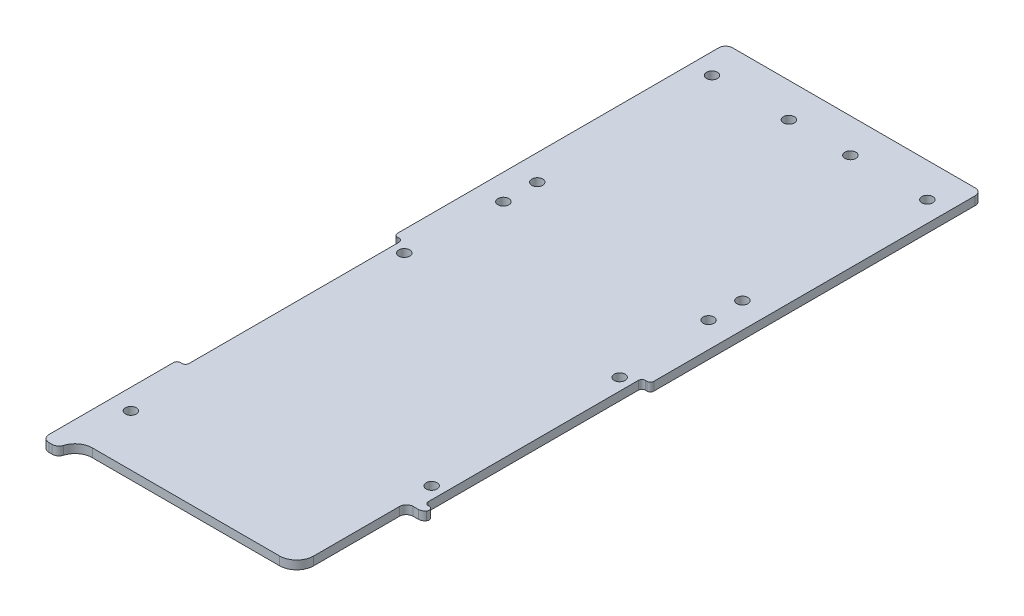
SolidWorks part; units mm, degrees
ref_plane "Front Plane" through (0, 0, 0) normal (0, 0, 1) x (1, 0, 0)
ref_plane "Top Plane" through (0, 0, 0) normal (0, 1, 0) x (1, 0, 0)
ref_plane "Right Plane" through (0, 0, 0) normal (1, 0, 0) x (0, 0, -1)
sketch "Sketch1" plane through (0, 0, 0) normal (0, 1, 0) x (1, 0, 0)
  line L0 (-39.9997, 0) -> (-39.9997, 114.3) construction
  line L1 (-47.625, 127) -> (47.625, 127)
  line L2 (-47.625, 127) -> (-47.625, -127)
  line L3 (-47.625, -127) -> (47.625, -127)
  line L4 (47.625, 127) -> (47.625, -127)
  line L5 (-47.625, 127) -> (47.625, -127) construction
  line L6 (-47.625, -127) -> (47.625, 127) construction
  line L7 (0, 0) -> (0, 127) construction
  line L8 (-39.9997, 0) -> (-39.9997, -101.6) construction
  line L9 (-39.9997, 0) -> (0, 0) construction
  line L10 (-41.275, -127) -> (-41.275, -120.65)
  line L11 (-41.275, -120.65) -> (41.275, -120.65)
  line L12 (41.275, -120.65) -> (41.275, -127)
  line L13 (-39.9997, 114.3) -> (-11.4247, 114.3) construction
  line L14 (39.9997, 114.3) -> (11.4247, 114.3) construction
  circle A0 centre (-39.9997, 114.3) radius 2.032
  circle A1 centre (-39.9997, 0) radius 2.032
  circle A2 centre (-39.9997, -101.6) radius 2.032
  circle A3 centre (39.9997, -101.6) radius 2.032
  circle A4 centre (39.9997, 0) radius 2.032
  circle A5 centre (39.9997, 114.3) radius 2.032
  circle A6 centre (-11.4247, 114.3) radius 2.032
  circle A7 centre (11.4247, 114.3) radius 2.032
  circle A8 centre (-39.9997, -69.85) radius 2.032
  circle A9 centre (39.9997, -69.85) radius 2.032
  point P0 (0, 0)
  dimension "D4" = 4.064
  dimension "D10" = 28.575
  dimension "D1" = 95.25
  dimension "D2" = 254
  dimension "D3" = 7.6253
  dimension "D5" = 12.7
  dimension "D6" = 25.4
  dimension "D7" = 6.35
  dimension "D8" = 6.35
  dimension "D9" = 6.35
  dimension "D11" = 69.85
extrude "Boss-Extrude1" add sketch "Sketch1" along normal blind 3.175 contours L4 L1 L2 L3 A4 A0 A1 A2 A3 A5 | A8 | A3 region at (0, 0, -2.6944) region at (39.9997, 0, 101.6) region at (-39.9997, 0, 69.85)
fillet "Fillet1" radius 2.54 4 edges at (-47.625, 1.5875, -127) (47.625, 1.5875, -127) (47.625, 1.5875, 127) (-47.625, 1.5875, 127)
fillet "Fillet2" radius 2.54 2 edges at (41.275, 1.5875, 127) (-41.275, 1.5875, 127)
fillet "Fillet3" radius 6.35 2 edges at (41.275, 1.5875, 120.65) (-41.275, 1.5875, 120.65)
sketch "Sketch2" plane through (0, 0, 0) normal (0, -1, 0) x (1, 0, 0)
  line L1 (43.815, 127) -> (45.085, 127) construction
  line L2 (40.6451, 123.5787) -> (40.6451, 79.8881)
  line L3 (40.6451, 79.8881) -> (47.625, 79.8881)
  line L11 (47.625, -124.46) -> (47.625, 124.46) construction
  line L12 (43.815, 127) -> (45.085, 127)
  line L13 (47.625, 79.8881) -> (47.625, 124.46)
  arc A0 (35.2956, 120.65) -> (41.3809, 125.1857) centre (35.2956, 127) ccw construction
  arc A1 (43.815, 127) -> (41.3809, 125.1857) centre (43.815, 124.46) ccw construction
  arc A2 (47.625, 124.46) -> (45.085, 127) centre (45.085, 124.46) ccw construction
  arc A3 (40.6451, 123.5787) -> (41.3809, 125.1857) centre (35.2956, 127) ccw
  arc A4 (43.815, 127) -> (41.3809, 125.1857) centre (43.815, 124.46) ccw
  arc A5 (47.625, 124.46) -> (45.085, 127) centre (45.085, 124.46) ccw
  dimension "D2" = 47.1119
  dimension "D1" = 6.9799
extrude "Cut-Extrude1" cut sketch "Sketch2" against normal through all
fillet "Fillet4" radius 6.35 1 edges at (40.6451, 1.5875, 123.5787)
fillet "Fillet5" radius 2.54 2 edges at (47.625, 1.5875, 79.8881) (40.6451, 1.5875, 79.8881)
sketch "Sketch3" plane through (0, 0, 0) normal (0, -1, 0) x (1, 0, 0)
  line L0 (-36.3022, -49.7791) -> (-39.909, -49.7791) construction
  line L1 (-40.417, -49.276) -> (-40.417, -45.7043) construction
  line L2 (-35.7942, -45.7043) -> (-35.7942, -49.276) construction
  line L3 (-39.909, -45.2013) -> (-36.3022, -45.2013) construction
  line L4 (-36.3022, -37.2027) -> (-39.909, -37.2027) construction
  line L5 (-35.7942, -33.1279) -> (-35.7942, -36.6996) construction
  line L6 (-40.417, -36.6996) -> (-40.417, -33.1279) construction
  line L7 (-39.909, -32.6249) -> (-36.3022, -32.6249) construction
  line L8 (36.291, -32.6249) -> (39.8978, -32.6249) construction
  line L9 (40.4058, -33.1279) -> (40.4058, -36.6996) construction
  line L10 (39.8978, -37.2027) -> (36.291, -37.2027) construction
  line L11 (35.783, -36.6996) -> (35.783, -33.1279) construction
  line L12 (36.291, -45.2013) -> (39.8978, -45.2013) construction
  line L13 (35.783, -49.276) -> (35.783, -45.7043) construction
  line L14 (40.4058, -45.7043) -> (40.4058, -49.276) construction
  line L15 (39.8978, -49.7791) -> (36.291, -49.7791) construction
  line L16 (-36.3022, -49.7791) -> (-39.909, -49.7791)
  line L17 (-40.417, -49.276) -> (-40.417, -45.7043)
  line L18 (-35.7942, -45.7043) -> (-35.7942, -49.276)
  line L19 (-39.909, -45.2013) -> (-36.3022, -45.2013)
  line L20 (-36.3022, -37.2027) -> (-39.909, -37.2027)
  line L21 (-35.7942, -33.1279) -> (-35.7942, -36.6996)
  line L22 (-40.417, -36.6996) -> (-40.417, -33.1279)
  line L23 (-39.909, -32.6249) -> (-36.3022, -32.6249)
  line L24 (36.291, -32.6249) -> (39.8978, -32.6249)
  line L25 (40.4058, -33.1279) -> (40.4058, -36.6996)
  line L26 (39.8978, -37.2027) -> (36.291, -37.2027)
  line L27 (35.783, -36.6996) -> (35.783, -33.1279)
  line L28 (36.291, -45.2013) -> (39.8978, -45.2013)
  line L29 (35.783, -49.276) -> (35.783, -45.7043)
  line L30 (40.4058, -45.7043) -> (40.4058, -49.276)
  line L31 (39.8978, -49.7791) -> (36.291, -49.7791)
  line L32 (-47.625, -25.836) -> (47.625, -25.836)
  line L33 (-47.625, -124.46) -> (-47.625, 124.46) construction
  line L34 (47.625, -124.46) -> (47.625, 77.3481) construction
  line L35 (0, -25.836) -> (0, -56.0686) construction
  line L1362 (-40.417, -34.9138) -> (-35.7942, -34.9138)
  line L1857 (-38.1056, -32.6249) -> (-38.1056, -37.2027)
  line L1858 (-38.1056, -45.2013) -> (-38.1056, -49.7791)
  line L1859 (-40.417, -47.4902) -> (-35.7942, -47.4902)
  circle A0 centre (-38.1056, -34.9138) radius 2.032
  circle A1 centre (-38.1056, -47.4902) radius 2.032
  circle A2 centre (38.1056, -47.4902) radius 2.032
  circle A3 centre (38.1056, -34.9138) radius 2.032
  ellipse E0 centre (-39.909, -45.7043) end of major axis (-39.401, -45.7043) minor radius 0.5031 (-39.909, -45.2013) -> (-40.417, -45.7043) ccw construction
  ellipse E1 centre (-39.909, -49.276) end of major axis (-39.401, -49.276) minor radius 0.5031 (-40.417, -49.276) -> (-39.909, -49.7791) ccw construction
  ellipse E6 centre (-36.3022, -49.276) end of major axis (-35.7942, -49.276) minor radius 0.5031 (-36.3022, -49.7791) -> (-35.7942, -49.276) ccw construction
  ellipse E7 centre (-36.3022, -45.7043) end of major axis (-35.7942, -45.7043) minor radius 0.5031 (-35.7942, -45.7043) -> (-36.3022, -45.2013) ccw construction
  ellipse E8 centre (-39.909, -36.6996) end of major axis (-39.401, -36.6996) minor radius 0.5031 (-40.417, -36.6996) -> (-39.909, -37.2027) ccw construction
  ellipse E9 centre (-36.3022, -36.6996) end of major axis (-35.7942, -36.6996) minor radius 0.5031 (-36.3022, -37.2027) -> (-35.7942, -36.6996) ccw construction
  ellipse E10 centre (-36.3022, -33.1279) end of major axis (-35.7942, -33.1279) minor radius 0.5031 (-35.7942, -33.1279) -> (-36.3022, -32.6249) ccw construction
  ellipse E11 centre (-39.909, -33.1279) end of major axis (-39.401, -33.1279) minor radius 0.5031 (-39.909, -32.6249) -> (-40.417, -33.1279) ccw construction
  ellipse E12 centre (39.8978, -33.1279) end of major axis (40.4058, -33.1279) minor radius 0.5031 (40.4058, -33.1279) -> (39.8978, -32.6249) ccw construction
  ellipse E13 centre (36.291, -33.1279) end of major axis (36.799, -33.1279) minor radius 0.5031 (36.291, -32.6249) -> (35.783, -33.1279) ccw construction
  ellipse E14 centre (39.8978, -36.6996) end of major axis (40.4058, -36.6996) minor radius 0.5031 (39.8978, -37.2027) -> (40.4058, -36.6996) ccw construction
  ellipse E15 centre (36.291, -36.6996) end of major axis (36.799, -36.6996) minor radius 0.5031 (35.783, -36.6996) -> (36.291, -37.2027) ccw construction
  ellipse E16 centre (36.291, -45.7043) end of major axis (36.799, -45.7043) minor radius 0.5031 (36.291, -45.2013) -> (35.783, -45.7043) ccw construction
  ellipse E17 centre (36.291, -49.276) end of major axis (36.799, -49.276) minor radius 0.5031 (35.783, -49.276) -> (36.291, -49.7791) ccw construction
  ellipse E18 centre (39.8978, -45.7043) end of major axis (40.4058, -45.7043) minor radius 0.5031 (40.4058, -45.7043) -> (39.8978, -45.2013) ccw construction
  ellipse E19 centre (39.8978, -49.276) end of major axis (40.4058, -49.276) minor radius 0.5031 (39.8978, -49.7791) -> (40.4058, -49.276) ccw construction
  ellipse E20 centre (-39.909, -45.7043) end of major axis (-39.401, -45.7043) minor radius 0.5031 (-39.909, -45.2013) -> (-40.417, -45.7043) ccw
  ellipse E21 centre (-39.909, -49.276) end of major axis (-39.401, -49.276) minor radius 0.5031 (-40.417, -49.276) -> (-39.909, -49.7791) ccw
  ellipse E22 centre (-36.3022, -49.276) end of major axis (-35.7942, -49.276) minor radius 0.5031 (-36.3022, -49.7791) -> (-35.7942, -49.276) ccw
  ellipse E23 centre (-36.3022, -45.7043) end of major axis (-35.7942, -45.7043) minor radius 0.5031 (-35.7942, -45.7043) -> (-36.3022, -45.2013) ccw
  ellipse E24 centre (-39.909, -36.6996) end of major axis (-39.401, -36.6996) minor radius 0.5031 (-40.417, -36.6996) -> (-39.909, -37.2027) ccw
  ellipse E25 centre (-36.3022, -36.6996) end of major axis (-35.7942, -36.6996) minor radius 0.5031 (-36.3022, -37.2027) -> (-35.7942, -36.6996) ccw
  ellipse E26 centre (-36.3022, -33.1279) end of major axis (-35.7942, -33.1279) minor radius 0.5031 (-35.7942, -33.1279) -> (-36.3022, -32.6249) ccw
  ellipse E27 centre (-39.909, -33.1279) end of major axis (-39.401, -33.1279) minor radius 0.5031 (-39.909, -32.6249) -> (-40.417, -33.1279) ccw
  ellipse E28 centre (39.8978, -33.1279) end of major axis (40.4058, -33.1279) minor radius 0.5031 (40.4058, -33.1279) -> (39.8978, -32.6249) ccw
  ellipse E29 centre (36.291, -33.1279) end of major axis (36.799, -33.1279) minor radius 0.5031 (36.291, -32.6249) -> (35.783, -33.1279) ccw
  ellipse E30 centre (39.8978, -36.6996) end of major axis (40.4058, -36.6996) minor radius 0.5031 (39.8978, -37.2027) -> (40.4058, -36.6996) ccw
  ellipse E31 centre (36.291, -36.6996) end of major axis (36.799, -36.6996) minor radius 0.5031 (35.783, -36.6996) -> (36.291, -37.2027) ccw
  ellipse E32 centre (36.291, -45.7043) end of major axis (36.799, -45.7043) minor radius 0.5031 (36.291, -45.2013) -> (35.783, -45.7043) ccw
  ellipse E33 centre (36.291, -49.276) end of major axis (36.799, -49.276) minor radius 0.5031 (35.783, -49.276) -> (36.291, -49.7791) ccw
  ellipse E34 centre (39.8978, -45.7043) end of major axis (40.4058, -45.7043) minor radius 0.5031 (40.4058, -45.7043) -> (39.8978, -45.2013) ccw
  ellipse E35 centre (39.8978, -49.276) end of major axis (40.4058, -49.276) minor radius 0.5031 (39.8978, -49.7791) -> (40.4058, -49.276) ccw
  dimension "D2" = 4.064
extrude "Cut-Extrude2" cut sketch "Sketch3" against normal through all contours A0 | A1 | A2 | A3
sketch "Sketch4" plane through (0, 3.175, 0) normal (0, 1, 0) x (1, 0, 0)
  line L11 (-47.625, 124.46) -> (-47.625, -124.46) construction
  line L12 (-47.625, -76.835) -> (-44.45, -76.835)
  line L13 (-47.625, -76.835) -> (-47.625, 3.81)
  line L15 (-47.625, 3.81) -> (-44.45, 3.81)
  line L16 (-44.45, -76.835) -> (-44.45, 3.81)
  line L17 (47.625, 124.46) -> (47.625, -77.3481) construction
  line L18 (47.625, -76.835) -> (44.45, -76.835)
  line L19 (47.625, -76.835) -> (47.625, 3.81)
  line L20 (47.625, 3.81) -> (44.45, 3.81)
  line L45 (44.45, -76.835) -> (44.45, 3.81)
  line L47 (43.1851, -79.8881) -> (45.085, -79.8881) construction
  dimension "D1" = 3.175
  dimension "D2" = 80.645
  dimension "D3" = 3.0531
extrude "Cut-Extrude3" cut sketch "Sketch4" against normal through all and the other way through all
fillet "Fillet6" radius 1.27 8 edges at (-44.45, 1.5875, -3.81) (-47.625, 1.5875, -3.81) (-47.625, 1.5875, 76.835) (-44.45, 1.5875, 76.835) (44.45, 1.5875, 76.835) (47.625, 1.5875, 76.835) (44.45, 1.5875, -3.81) (47.625, 1.5875, -3.81)
